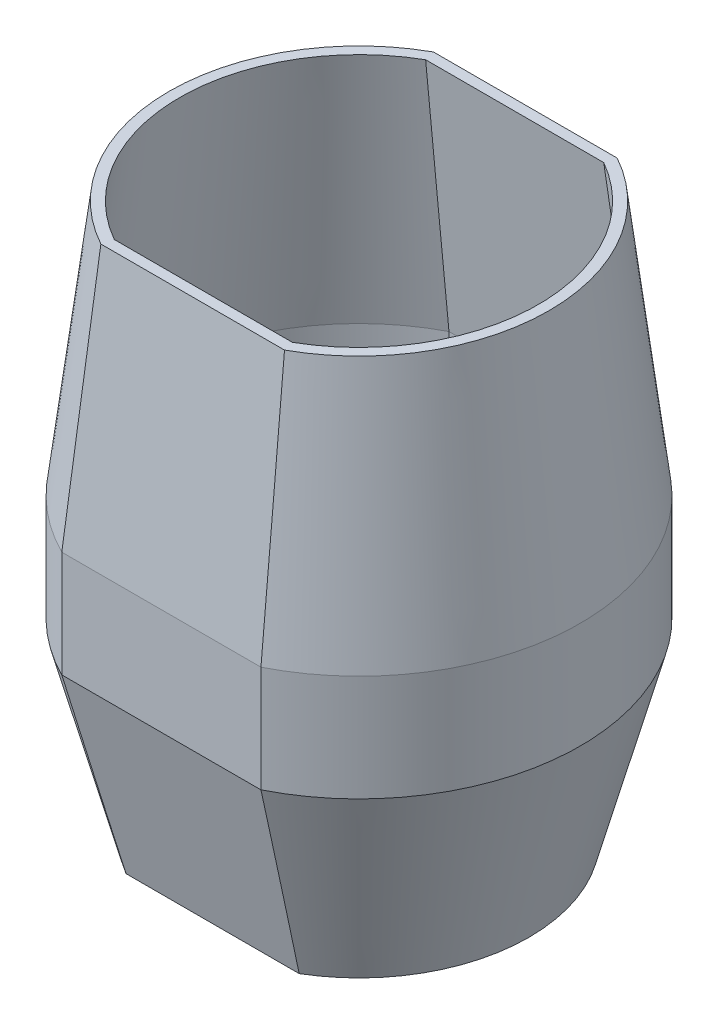
SolidWorks part; units mm, degrees
ref_plane "Front Plane" through (0, 0, 0) normal (0, 0, 1) x (1, 0, 0)
ref_plane "Top Plane" through (0, 0, 0) normal (0, 1, 0) x (1, 0, 0)
ref_plane "Right Plane" through (0, 0, 0) normal (1, 0, 0) x (0, 0, -1)
sketch "Sketch1" plane through (0, 0, 0) normal (0, 1, 0) x (1, 0, 0)
  line L0 (-40.7139, 68.8649) -> (40.7139, 68.8649)
  line L1 (-39.3227, -63.8649) -> (39.3227, -63.8649)
  line L3 (-39.3227, 63.8649) -> (39.3227, 63.8649)
  line L5 (-92.35, -78.8) -> (92.35, 78.8) construction
  line L6 (-92.35, 78.8) -> (92.35, -78.8) construction
  line L7 (-40.7139, -68.8649) -> (40.7139, -68.8649)
  arc A0 (-39.3227, 63.8649) -> (-39.3227, -63.8649) centre (0, 0) ccw
  arc A1 (39.3227, -63.8649) -> (39.3227, 63.8649) centre (0, 0) ccw
  arc A2 (40.7139, -68.8649) -> (40.7139, 68.8649) centre (0, 0) ccw
  arc A3 (-40.7139, 68.8649) -> (-40.7139, -68.8649) centre (0, 0) ccw
  point P0 (0, 0)
  dimension "D3" = 5
  dimension "D4" = 80
  dimension "D1" = 184.7
  dimension "D2" = 157.6
extrude "Boss-Extrude1" add sketch "Sketch1" along normal blind 90 draft 15 contours L0 A2 L7 A3 draft outward yes
extrude "Cut-Extrude1" cut sketch "Sketch1<4>" along normal blind 90 draft 15 contours A0 L1 A1 L3 draft outward yes
sketch "Sketch1<4>" plane through (0, 0, 0) normal (0, 1, 0) x (1, 0, 0) same geometry as "Sketch1"
sketch "Sketch2" plane through (0, 0, 0) normal (0, 1, 0) x (1, 0, 0)
  circle A0 centre (0, 0) radius 28.6941
sketch "Sketch3" plane through (0, 90, 0) normal (0, 1, 0) x (1, 0, 0)
  line L0 (-45.6435, -87.9803) -> (45.6435, -87.9803) construction
  line L1 (-45.6435, 87.9803) -> (45.6435, 87.9803) construction
  line L2 (-46.8474, -92.9803) -> (46.8474, -92.9803)
  line L3 (46.8474, 92.9803) -> (-46.8474, 92.9803)
  line L4 (-46.8474, -92.9803) -> (46.8474, -92.9803)
  line L5 (46.8474, 92.9803) -> (-46.8474, 92.9803)
  line L6 (-45.6435, -87.9803) -> (45.6435, -87.9803)
  line L7 (-45.6435, 87.9803) -> (45.6435, 87.9803)
  arc A0 (45.6435, -87.9803) -> (45.6435, 87.9803) centre (0, 0) ccw construction
  arc A1 (-45.6435, 87.9803) -> (-45.6435, -87.9803) centre (0, 0) ccw construction
  arc A2 (-46.8474, 92.9803) -> (-46.8474, -92.9803) centre (0, 0) ccw
  arc A3 (46.8474, -92.9803) -> (46.8474, 92.9803) centre (0, 0) ccw
  arc A4 (-46.8474, 92.9803) -> (-46.8474, -92.9803) centre (0, 0) ccw
  arc A5 (46.8474, -92.9803) -> (46.8474, 92.9803) centre (0, 0) ccw
  arc A6 (45.6435, -87.9803) -> (45.6435, 87.9803) centre (0, 0) ccw
  arc A7 (-45.6435, 87.9803) -> (-45.6435, -87.9803) centre (0, 0) ccw
  dimension "D1" = 0
extrude "Boss-Extrude3" add sketch "Sketch3" along normal blind 50 contours A4 L4 A5 L5 | A7 L6 A6 L7
sketch "Sketch4" plane through (0, 140, 0) normal (0, 1, 0) x (1, 0, 0)
  line L0 (-45.6435, -87.9803) -> (45.6435, -87.9803) construction
  line L1 (-45.6435, 87.9803) -> (45.6435, 87.9803) construction
  line L2 (46.8474, 92.9803) -> (-46.8474, 92.9803)
  line L3 (-46.8474, -92.9803) -> (46.8474, -92.9803)
  line L4 (46.8474, 92.9803) -> (-46.8474, 92.9803)
  line L5 (-46.8474, -92.9803) -> (46.8474, -92.9803)
  line L6 (-45.6435, -87.9803) -> (45.6435, -87.9803)
  line L7 (-45.6435, 87.9803) -> (45.6435, 87.9803)
  arc A0 (45.6435, -87.9803) -> (45.6435, 87.9803) centre (0, 0) ccw construction
  arc A1 (-45.6435, 87.9803) -> (-45.6435, -87.9803) centre (0, 0) ccw construction
  arc A2 (-46.8474, 92.9803) -> (-46.8474, -92.9803) centre (0, 0) ccw
  arc A3 (46.8474, -92.9803) -> (46.8474, 92.9803) centre (0, 0) ccw
  arc A4 (-46.8474, 92.9803) -> (-46.8474, -92.9803) centre (0, 0) ccw
  arc A5 (46.8474, -92.9803) -> (46.8474, 92.9803) centre (0, 0) ccw
  arc A6 (45.6435, -87.9803) -> (45.6435, 87.9803) centre (0, 0) ccw
  arc A7 (-45.6435, 87.9803) -> (-45.6435, -87.9803) centre (0, 0) ccw
  dimension "D1" = 0
extrude "Boss-Extrude4" add sketch "Sketch4" along normal blind 120 draft 7 contours A4 L5 A5 L4
extrude "Cut-Extrude2" cut sketch "Sketch4<3>" along normal blind 160 draft 7 contours A7 L6 A6 L7
sketch "Sketch4<3>" plane through (0, 140, 0) normal (0, 1, 0) x (1, 0, 0) same geometry as "Sketch4"
